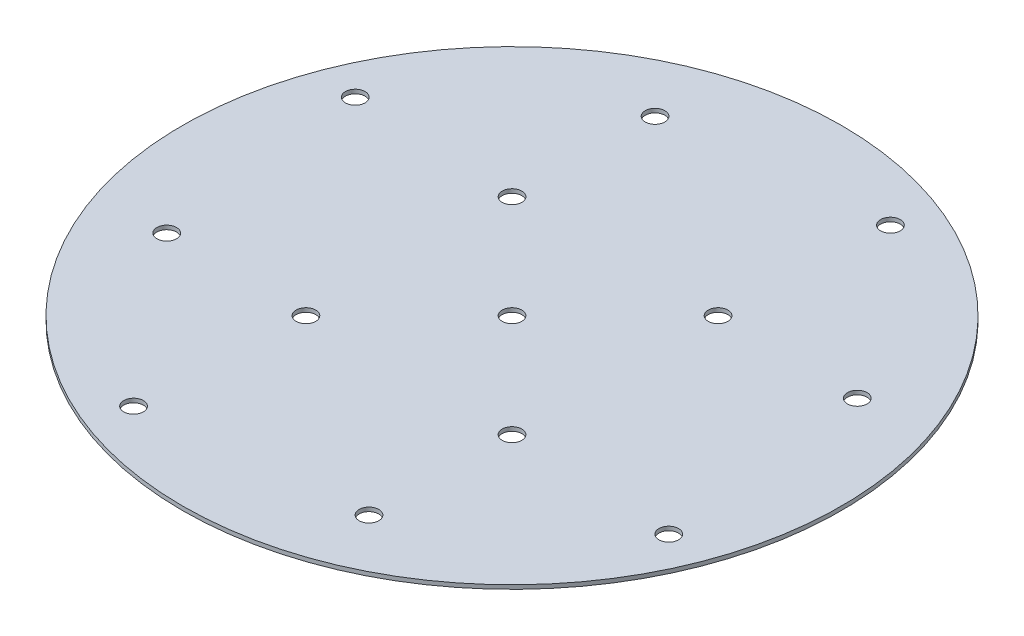
SolidWorks part; units mm, degrees
material "6061-T6 (SS)"
ref_plane "Front Plane" through (0, 0, 0) normal (0, 0, 1) x (1, 0, 0)
ref_plane "Top Plane" through (0, 0, 0) normal (0, 1, 0) x (1, 0, 0)
ref_plane "Right Plane" through (0, 0, 0) normal (1, 0, 0) x (0, 0, -1)
sketch "Sketch2" plane through (0, 0, 0) normal (1, 0, 0) x (0, 0, -1)
  line L0 (0, 0) -> (-82.55, 0)
  line L1 (-82.55, 0) -> (-82.55, 1)
  line L2 (-82.55, 1) -> (0, 1)
  line L5 (0, 1) -> (0, 0)
  dimension "D1" = 82.55
  dimension "D2" = 1
ref_axis "Axis1" through (0, -0.05, 0) along (0, 1, 0)
revolve "Revolve1" add sketch "Sketch2" angle 360 about axis through (0, -0.05, 0) along (0, 1, 0)
hole_wizard "#10 (0.1935) Diameter Hole1" positions "Sketch6" profile "Sketch7" hole size "#10" standard "ANSI Inch" end condition through all
sketch "Sketch6" plane through (0, 1, 0) normal (0, 1, 0) x (1, 0, 0)
  line L0 (0, 0) -> (-53.438, 129.0108) construction
  line L2 (0, 0) -> (0, 109.0908) construction
  line L3 (0, 0) -> (-76.2663, 31.5905) construction
  line L4 (0, 0) -> (-47.7784, 47.7784) construction
  circle A0 centre (0, 0) radius 82.55 construction
  point P0 (-25.3336, 61.1608)
  point P11 (264.7437, 73.7878)
  point P20 (-67.0275, 27.7637)
  point P22 (-25.8094, 25.8094)
  dimension "D1" = 22.5
  dimension "D2" = 66.2
  dimension "D3" = 72.55
  dimension "D4" = 45
  dimension "D6" = 22.5
  dimension "D5" = 36.5
sketch "Sketch7" plane through (-25.3336, 1, -61.1608) normal (1, 0, 0) x (0, 0, 1)
  line L0 (0, 0) -> (0, 1)
  line L1 (0, 1) -> (2.4574, 1)
  line L2 (2.4574, 1) -> (2.4574, 0)
  line L5 (2.4574, 0) -> (0, 0)
  line L11 (0, -6.35) -> (0, 107.95) construction
  dimension "Thru Hole Dia." = 4.9149
  dimension "Thru Hole Depth" = 1
pattern_circular "CirPattern3" count 4 over 360 about axis through (0, -0.05, 0) along (0, 1, 0) of "#10 (0.1935) Diameter Hole1"
hole_wizard "#10 (0.1935) Diameter Hole2" positions "Sketch8" profile "Sketch9" hole size "#10" standard "ANSI Inch" end condition through all
sketch "Sketch8" plane through (0, 1, 0) normal (0, 1, 0) x (1, 0, 0)
  line L0 (0, 0) -> (106.3094, -1.7118) construction
  point P7 (0, 0)
sketch "Sketch9" plane through (0, 1, 0) normal (1, 0, 0) x (0, 0, 1)
  line L0 (0, 0) -> (0, 1)
  line L1 (0, 1) -> (2.4574, 1)
  line L2 (2.4574, 1) -> (2.4574, 0)
  line L5 (2.4574, 0) -> (0, 0)
  line L11 (0, -6.35) -> (0, 107.95) construction
  dimension "Thru Hole Dia." = 4.9149
  dimension "Thru Hole Depth" = 1
equation "\"TubeDiameter\" = 6.500in"
equation "\"D1@Sketch2\"=\"TubeDiameter\"/2"
equation "\"D2@Sketch6\"=66.2"
equation "\"D3@Sketch6\"=\"TubeDiameter\"/2-10mm"
